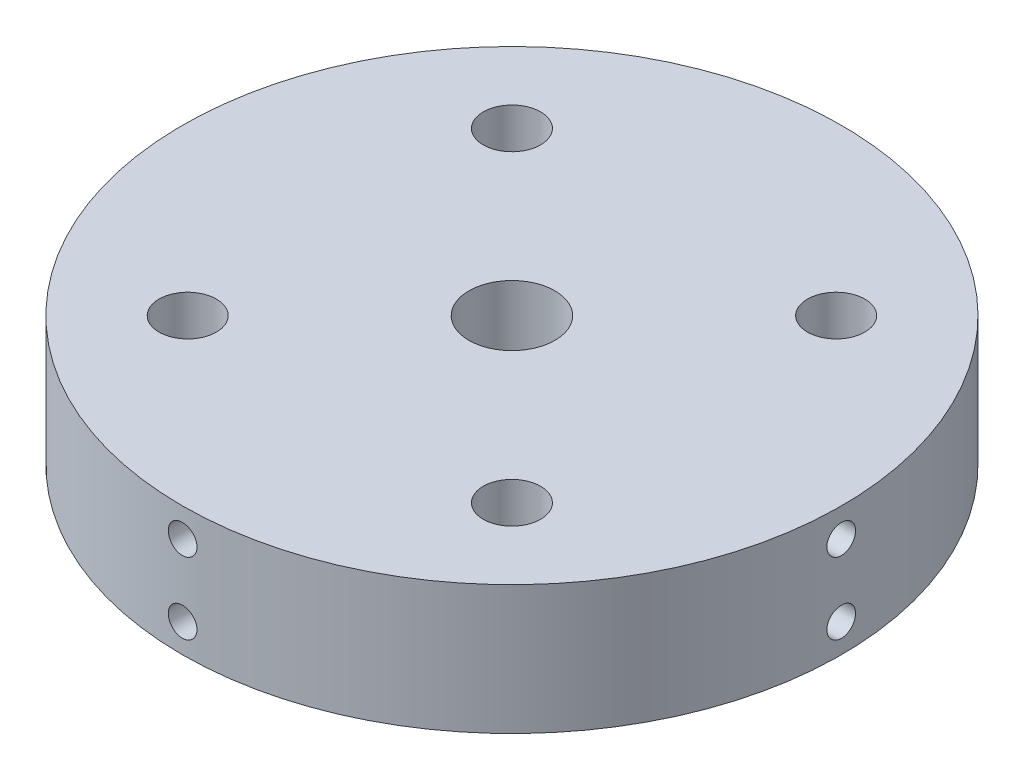
SolidWorks part; units mm, degrees
material "6061-T6 (SS)"
ref_plane "Front Plane" through (0, 0, 0) normal (0, 0, 1) x (1, 0, 0)
ref_plane "Top Plane" through (0, 0, 0) normal (0, 1, 0) x (1, 0, 0)
ref_plane "Right Plane" through (0, 0, 0) normal (1, 0, 0) x (0, 0, -1)
sketch "Sketch1" plane through (0, 0, 0) normal (0, 1, 0) x (1, 0, 0)
  circle A0 centre (0, 0) radius 73.025
  dimension "D1" = 146.05
extrude "Boss-Extrude1" add sketch "Sketch1" along normal blind 28.575
sketch "Sketch2" plane through (0, 28.575, 0) normal (0, 1, 0) x (1, 0, 0)
  circle A0 centre (0, 0) radius 9.525
  dimension "D1" = 19.05
extrude "Cut-Extrude1" cut sketch "Sketch2" against normal through all
ref_plane "Plane1" through (0, 0, 73.025) normal (0, 0, 1) x (1, 0, 0)
ref_plane "Plane2" through (0, 0, -73.025) normal (0, 0, 1) x (1, 0, 0)
sketch "Sketch30" plane through (0, 0, 73.025) normal (0, 0, 1) x (1, 0, 0)
  line L0 (0, 30.5674) -> (0, -2.7265) construction
  line L1 (73.025, 28.575) -> (-73.025, 28.575) construction
  circle A0 centre (0, 22.225) radius 3.175
  circle A1 centre (0, 6.35) radius 3.175
  dimension "D1" = 6.35
  dimension "D2" = 6.35
  dimension "D3" = 15.875
  dimension "D4" = 6.35
extrude "Cut-Extrude2" cut sketch "Sketch30" against normal blind 25.4
pattern_circular "CirPattern3" count 4 over 360 about axis through (0, 28.575, 0) along (0, -1, 0) of "Cut-Extrude2" reverse direction yes
sketch "Sketch31" plane through (0, 28.575, 0) normal (0, 1, 0) x (1, 0, 0)
  line L0 (0, 73.025) -> (0, -73.025) construction
  line L1 (-73.025, 0) -> (73.025, 0) construction
  line L2 (51.6365, 51.6365) -> (-51.6365, -51.6365) construction
  line L3 (-51.6365, 51.6365) -> (51.6365, -51.6365) construction
  circle A0 centre (0, 0) radius 73.025 construction
  circle A1 centre (35.921, 35.921) radius 6.35
  dimension "D4" = 12.7
  dimension "D1" = 50.8
  dimension "D2" = 45
  dimension "D3" = 45
extrude "Cut-Extrude3" cut sketch "Sketch31" against normal through all
pattern_circular "CirPattern4" count 4 over 360 about axis through (0, 28.575, 0) along (0, -1, 0) of "Cut-Extrude3"
